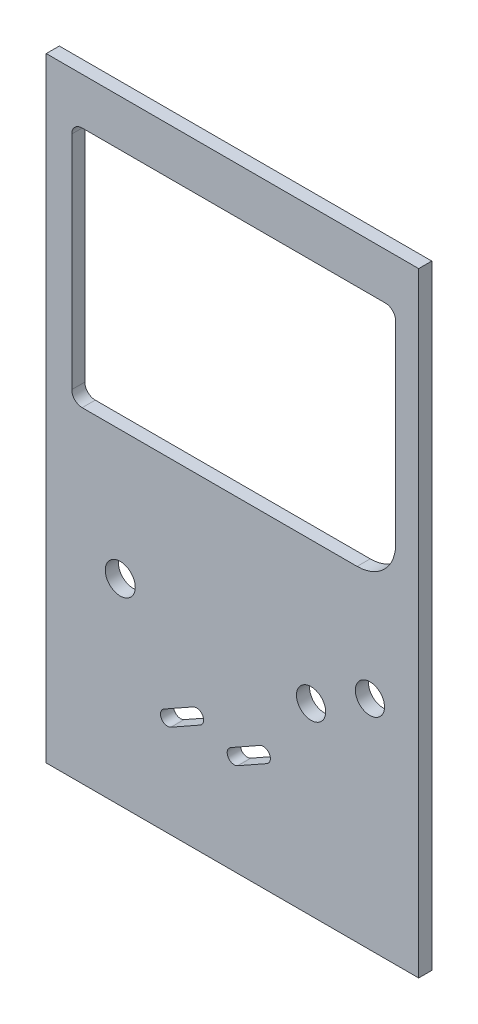
SolidWorks part; units mm, degrees
ref_plane "Front Plane" through (0, 0, 0) normal (0, 0, 1) x (1, 0, 0)
ref_plane "Top Plane" through (0, 0, 0) normal (0, 1, 0) x (1, 0, 0)
ref_plane "Right Plane" through (0, 0, 0) normal (1, 0, 0) x (0, 0, -1)
sketch "Sketch1" plane through (0, 0, 0) normal (0, 0, 1) x (1, 0, 0)
  line L1 (-26.2308, 73.6471) -> (38.6518, 73.6471)
  line L3 (-44.6471, -70.649) -> (-44.6471, 70.649)
  line L5 (27.0934, -73.6471) -> (-41.649, -73.6471)
  line L7 (-24.0867, 73.6955) -> (-35.6911, 73.6955)
  line L15 (-16.3293, -29.1587) -> (-16.3293, -23.8757)
  line L19 (44.6471, 67.6705) -> (44.6471, -53.896)
  line L20 (-0.4012, -48.3225) -> (6.5714, -44.4005)
  line L21 (8.2266, -47.343) -> (1.254, -51.2651)
  line L22 (-44.6471, 73.6471) -> (44.6471, 73.6471)
  line L23 (44.6471, 73.6471) -> (44.6471, -73.6471)
  line L24 (44.6471, -73.6471) -> (-44.6471, -73.6471)
  line L25 (-44.6471, -73.6471) -> (-44.6471, 73.6471)
  line L26 (-25.1679, 56.2163) -> (-25.1679, 10.288)
  line L27 (-25.1679, 10.288) -> (24.9222, 10.288)
  line L28 (24.9222, 10.288) -> (24.9222, 56.2163)
  line L29 (24.9222, 56.2163) -> (-25.1679, 56.2163)
  line L34 (36.6393, 62.5051) -> (-36.0272, 62.5051)
  line L35 (-38.5272, 60.0051) -> (-38.5272, 6.9331)
  line L36 (-36.0272, 4.4331) -> (29.8893, 4.4331)
  line L37 (39.1393, 13.6831) -> (39.1393, 60.0051)
  line L38 (-16.4012, -48.3225) -> (-9.4286, -44.4005)
  line L39 (-7.7734, -47.343) -> (-14.746, -51.2651)
  line L41 (44.6471, 70.649) -> (44.6471, 67.6705)
  line L43 (38.6518, 73.6471) -> (41.649, 73.6471)
  line L45 (-41.649, 73.6471) -> (-26.2308, 73.6471)
  line L150 (42.2525, -55.0539) -> (42.2511, -54.9499)
  circle A0 centre (34.1495, 24.0914) radius 10.7
  circle A2 centre (-26.9008, -26.5172) radius 3.6
  arc A3 (8.2266, -47.343) -> (6.5714, -44.4005) centre (7.399, -45.8717) ccw
  arc A6 (-16.4012, -48.3225) -> (-14.746, -51.2651) centre (-15.5736, -49.7938) ccw
  arc A7 (-7.7734, -47.343) -> (-9.4286, -44.4005) centre (-8.601, -45.8717) ccw
  circle A15 centre (18.8495, -29.5462) radius 3.5
  circle A16 centre (32.9602, -21.4767) radius 3.5
  arc A17 (-0.4012, -48.3225) -> (1.254, -51.2651) centre (0.4264, -49.7938) ccw
  circle A19 centre (-32.9539, 40.3411) radius 4.5
  arc A24 (39.1393, 60.0051) -> (36.6393, 62.5051) centre (36.6393, 60.0051) ccw
  arc A25 (-36.0272, 62.5051) -> (-38.5272, 60.0051) centre (-36.0272, 60.0051) ccw
  arc A26 (-38.5272, 6.9331) -> (-36.0272, 4.4331) centre (-36.0272, 6.9331) ccw
  arc A27 (29.8893, 4.4331) -> (39.1393, 13.6831) centre (29.8893, 13.6831) ccw
  ellipse E3 centre (-41.649, -70.649) end of major axis (-39.5276, -72.7703) minor radius 2.9963 (-44.6471, -70.649) -> (-41.649, -73.6471) ccw
  ellipse E5 centre (41.649, 70.649) end of major axis (39.5276, 72.7703) minor radius 2.9963 (44.6471, 70.649) -> (41.649, 73.6471) ccw
  ellipse E7 centre (-41.649, 70.649) end of major axis (-43.7703, 68.5276) minor radius 2.9963 (-41.649, 73.6471) -> (-44.6471, 70.649) ccw
  spline S1 degree 3 poles (44.6485, -54) (44.663, -55.258) (44.5568, -56.5068) (44.2157, -58.3662) (44.0715, -58.9837) (43.7192, -60.2138) (43.5128, -60.8202) (42.8075, -62.6008) (42.2221, -63.7422) (41.3373, -65.1085) (41.1525, -65.3788) (40.7717, -65.907) (40.5751, -66.1657) (39.9672, -66.9256) (39.1083, -67.8961) (38.1523, -68.7812) (37.1464, -69.6222) (36.6152, -70.0225) (34.9811, -71.1285) (33.8311, -71.748) (32.3187, -72.3766) (32.0124, -72.495) (31.3922, -72.7168) (31.0776, -72.8204) (30.1333, -73.105) (29.5001, -73.2613) (27.5898, -73.6337) (26.302, -73.7542) (25, -73.7456) knots 0 0 0 0 0.125 0.125 0.1875 0.1875 0.25 0.25 0.375 0.375 0.40625 0.40625 0.4375 0.4375 0.5 0.5625 0.5625 0.625 0.625 0.75 0.75 0.78125 0.78125 0.8125 0.8125 0.875 0.875 1 1 1 1
  dimension "D4" = 21.4
  dimension "D8" = 7
  dimension "D11" = 9
  dimension "D12" = 7.2
  dimension "D1" = 10.4977
  dimension "D2" = 89.2943
  dimension "D3" = 147.2943
  dimension "D5" = 25.9097
  dimension "D6" = 8.0696
  dimension "D7" = 14.1107
  dimension "D9" = 7.7861
  dimension "D10" = 22.1641
  dimension "D13" = 10.5715
extrude "Boss-Extrude1" add sketch "Sketch1" along normal blind 3.14 contours S1 L23 L19 A0 L37 A27 L36 A26 L35 A25 L34 A24 E5 L22 L1 E7 L3 E3 L5 A17 L20 A3 L21 A16 A15 A7 L39 A6 L38 A2 | E5 L23 L22 | E7 L22 L25 | E3 L25 L24 | L23 S1 L24 | L23 A0 L37 region at (-0.9227, -16.9165, 0) region at (-43.9765, 72.9765, 0) region at (43.9765, 72.9765, 0) region at (-43.9765, -72.9765, 0) region at (41.4616, 24.0914, 0) region at (40.3936, -69.2915, 0)
